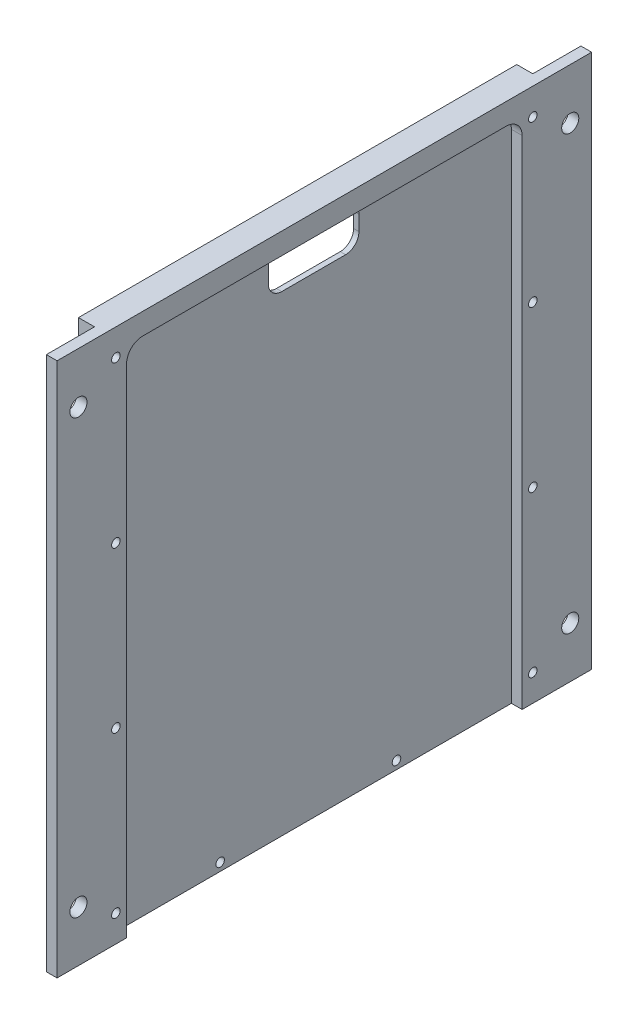
SolidWorks part; units mm, degrees
material "6061-T6 (SS)"
ref_plane "Front Plane" through (0, 0, 0) normal (0, 0, 1) x (1, 0, 0)
ref_plane "Top Plane" through (0, 0, 0) normal (0, 1, 0) x (1, 0, 0)
ref_plane "Right Plane" through (0, 0, 0) normal (1, 0, 0) x (0, 0, -1)
ref_plane "Plane1" through (4.25, 0, 0) normal (1, 0, 0) x (0, 0, -1)
sketch "Sketch1" plane through (4.25, 0, 0) normal (1, 0, 0) x (0, 0, -1)
  line L0 (-4.25, 0) -> (4.25, 0)
  line L1 (4.25, 0) -> (4.25, 227)
  line L2 (4.25, 227) -> (-4.25, 227)
  line L3 (-4.25, 227) -> (-4.25, 0)
  dimension "D1" = 227
  dimension "D2" = 8.5
  dimension "D3" = 4.25
  dimension "D4" = 227
extrude "Boss-Extrude1" add sketch "Sketch1" against normal blind 8.5
ref_plane "Plane2" through (-4.25, 0, 0) normal (-1, 0, 0) x (0, -1, 0)
sketch "Sketch2" plane through (-4.25, 0, 0) normal (-1, 0, 0) x (0, -1, 0)
  line L0 (-6.5, -87.25) -> (-6.5, -4.25)
  line L1 (-6.5, -4.25) -> (-220.5, -4.25)
  line L2 (-220.5, -4.25) -> (-220.5, -87.25)
  line L3 (-220.5, -87.25) -> (-227, -87.25)
  line L4 (-227, -87.25) -> (-227, -95.75)
  line L5 (-227, -95.75) -> (0, -95.75)
  line L6 (0, -95.75) -> (0, -87.25)
  line L7 (0, -87.25) -> (-6.5, -87.25)
  line L8 (0, -4.25) -> (-227, -4.25) construction
  dimension "D1" = 91.5
  dimension "D2" = 6.5
  dimension "D3" = 83
  dimension "D4" = 8.5
  dimension "D5" = 214
extrude "Boss-Extrude2" add sketch "Sketch2" against normal blind 2
sketch "Sketch3" plane through (-2.25, 0, 0) normal (1, 0, 0) x (0, 0, -1)
  line L0 (87.25, 0) -> (87.25, 227)
  line L1 (87.25, 227) -> (95.75, 227)
  line L2 (95.75, 227) -> (95.75, 0)
  line L3 (95.75, 0) -> (87.25, 0)
extrude "Boss-Extrude3" add sketch "Sketch3" along normal blind 6.5
ref_plane "Z_midplane" through (0, 113.5, 0) normal (0, 1, 0) x (1, 0, 0)
sketch "Sketch4" plane through (-4.25, 0, 0) normal (-1, 0, 0) x (0, 0, 1)
  line L0 (-4.75, 6.5) -> (-86.75, 6.5)
  line L1 (-86.75, 6.5) -> (-86.75, 220.5)
  line L2 (-86.75, 220.5) -> (-4.75, 220.5)
  line L3 (-4.75, 220.5) -> (-4.75, 6.5)
extrude "Boss-Extrude4" add sketch "Sketch4" along normal blind 3
sketch "Sketch5" plane through (-2.25, 0, 0) normal (1, 0, 0) x (0, 0, -1)
  line L0 (8.75, 10.5) -> (82.75, 10.5)
  line L1 (82.75, 10.5) -> (82.75, 216.5)
  line L2 (82.75, 216.5) -> (8.75, 216.5)
  line L3 (8.75, 216.5) -> (8.75, 10.5)
  line L4 (87.25, 6.5) -> (4.25, 6.5) construction
  line L5 (4.75, 6.5) -> (4.75, 220.5) construction
  line L6 (86.75, 220.5) -> (86.75, 6.5) construction
  line L7 (4.75, 220.5) -> (86.75, 220.5) construction
  dimension "D1" = 4
  dimension "D2" = 4
  dimension "D3" = 4
  dimension "D4" = 4
extrude "Cut-Extrude1" cut sketch "Sketch5" against normal through all
hole_wizard "M2x0.4 Tapped Hole1" positions "Sketch27" profile "Sketch26" tap size "M2x0.4" standard "ANSI Metric" end condition through all
sketch "Sketch27" plane through (-7.25, 0, 0) normal (-1, 0, 0) x (0, 0, 1)
  line L0 (-86.75, 6.5) -> (-4.75, 6.5) construction
  line L2 (-45.75, 10.5) -> (-45.75, 216.5) construction
  line L3 (-8.75, 10.5) -> (-82.75, 10.5) construction
  line L4 (-82.75, 216.5) -> (-8.75, 216.5) construction
  line L6 (-8.75, 113.5) -> (-82.75, 113.5) construction
  line L7 (-8.75, 216.5) -> (-8.75, 10.5) construction
  line L8 (-82.75, 10.5) -> (-82.75, 216.5) construction
  line L9 (-8.75, 11.5) -> (-4.75, 11.5) construction
  line L10 (-4.75, 6.5) -> (-4.75, 220.5) construction
  point P0 (-6.75, 11.5)
  point P31 (-6.75, 41.5)
  point P32 (-6.75, 71.5)
  point P33 (-6.75, 101.5)
  point P54 (-84.75, 11.5)
  point P55 (-84.75, 41.5)
  point P56 (-84.75, 71.5)
  point P57 (-84.75, 101.5)
  point P60 (-84.75, 125.5)
  point P61 (-84.75, 155.5)
  point P62 (-84.75, 185.5)
  point P63 (-84.75, 215.5)
  point P65 (-6.75, 125.5)
  point P66 (-6.75, 155.5)
  point P67 (-6.75, 185.5)
  point P68 (-6.75, 215.5)
  point P81 (-6.75, 11.5)
  dimension "D1" = 5
  dimension "D4" = 30
  dimension "D3" = 4
sketch "Sketch26" plane through (-7.25, 11.5, -6.75) normal (0, 1, 0) x (0, 0, 1)
  line L0 (0, 0) -> (0, 11.5)
  line L1 (0, 11.5) -> (0.8, 11.5)
  line L2 (0.8, 11.5) -> (0.8, 0)
  line L5 (0.8, 0) -> (0, 0)
  line L11 (0, -6.35) -> (0, 107.95) construction
  dimension "Thru Tap Drill Dia." = 1.6
  dimension "Thru Tap Drill Depth" = 11.5
cosmetic thread "Hole Thread1" parameters "D2"=2
cosmetic thread "Hole Thread2" parameters "D2"=2
cosmetic thread "Hole Thread3" parameters "D2"=2
cosmetic thread "Hole Thread4" parameters "D2"=2
cosmetic thread "Hole Thread5" parameters "D2"=2
cosmetic thread "Hole Thread6" parameters "D2"=2
cosmetic thread "Hole Thread7" parameters "D2"=2
cosmetic thread "Hole Thread8" parameters "D2"=2
cosmetic thread "Hole Thread9" parameters "D2"=2
cosmetic thread "Hole Thread10" parameters "D2"=2
cosmetic thread "Hole Thread11" parameters "D2"=2
cosmetic thread "Hole Thread12" parameters "D2"=2
cosmetic thread "Hole Thread13" parameters "D2"=2
cosmetic thread "Hole Thread14" parameters "D2"=2
cosmetic thread "Hole Thread15" parameters "D2"=2
cosmetic thread "Hole Thread16" parameters "D2"=2
fillet "Fillet2" radius 3 4 edges at (-4.75, 10.5, -8.75) (-4.75, 216.5, -82.75) (-4.75, 216.5, -8.75) (-4.75, 10.5, -82.75) tangent propagation no
fillet "Fillet12" radius 2 1 edges type face fillet first side face at (-6.5, 140.25, -86.75) second side face at (-4.75, 6.5, -45.8125)
ref_plane "Y_midplane" through (0, 0, -45.75) normal (0, 0, 1) x (1, 0, 0)
sketch "Sketch43" plane through (-7.25, 0, 0) normal (-1, 0, 0) x (0, 0, 1)
  line L0 (-45.75, 10.5) -> (-45.75, 216.5) construction
  line L1 (-27.75, 10.5) -> (-30.75, 10.5)
  line L2 (-27.75, 10.5) -> (-27.75, 216.5)
  line L3 (-27.75, 216.5) -> (-30.75, 216.5)
  line L4 (-30.75, 10.5) -> (-30.75, 216.5)
  line L5 (-11.75, 10.5) -> (-79.75, 10.5) construction
  line L6 (-79.75, 216.5) -> (-11.75, 216.5) construction
  line L7 (-63.75, 10.5) -> (-60.75, 10.5)
  line L8 (-63.75, 10.5) -> (-63.75, 216.5)
  line L9 (-63.75, 216.5) -> (-60.75, 216.5)
  line L10 (-60.75, 10.5) -> (-60.75, 216.5)
  dimension "D1" = 3
  dimension "D2" = 30
extrude "Boss-Extrude6" add sketch "Sketch43" against normal blind 3
sketch "Sketch44" plane through (-7.25, 0, 0) normal (-1, 0, 0) x (0, 0, 1)
  line L0 (-8.75, 213.5) -> (-8.75, 13.5) construction
  line L1 (-8.75, 35.8) -> (-82.75, 35.8)
  line L2 (-8.75, 35.8) -> (-8.75, 38.8)
  line L3 (-8.75, 38.8) -> (-82.75, 38.8)
  line L4 (-82.75, 35.8) -> (-82.75, 38.8)
  line L5 (-8.75, 75.8) -> (-82.75, 75.8)
  line L6 (-8.75, 75.8) -> (-8.75, 78.8)
  line L7 (-8.75, 78.8) -> (-82.75, 78.8)
  line L8 (-82.75, 75.8) -> (-82.75, 78.8)
  line L9 (-8.75, 103.5) -> (-82.75, 103.5)
  line L10 (-8.75, 103.5) -> (-8.75, 106.5)
  line L11 (-8.75, 106.5) -> (-82.75, 106.5)
  line L12 (-82.75, 103.5) -> (-82.75, 106.5)
  line L13 (-82.75, 13.5) -> (-82.75, 213.5) construction
  line L14 (-84.75, 6.5) -> (-4.75, 6.5) construction
  line L15 (-8.75, 113.5) -> (-82.75, 113.5) construction
  line L16 (-8.75, 191.2) -> (-8.75, 188.2)
  line L17 (-8.75, 191.2) -> (-82.75, 191.2)
  line L18 (-82.75, 191.2) -> (-82.75, 188.2)
  line L19 (-8.75, 188.2) -> (-82.75, 188.2)
  line L20 (-8.75, 151.2) -> (-8.75, 148.2)
  line L21 (-8.75, 151.2) -> (-82.75, 151.2)
  line L22 (-82.75, 151.2) -> (-82.75, 148.2)
  line L23 (-8.75, 148.2) -> (-82.75, 148.2)
  line L24 (-8.75, 123.5) -> (-8.75, 120.5)
  line L25 (-8.75, 123.5) -> (-82.75, 123.5)
  line L26 (-82.75, 123.5) -> (-82.75, 120.5)
  line L27 (-8.75, 120.5) -> (-82.75, 120.5)
  dimension "D1" = 3
  dimension "D2" = 29.3
  dimension "D3" = 40
  dimension "D4" = 100
extrude "Boss-Extrude7" add sketch "Sketch44" against normal up to surface (3 mm away) up to face at (-4.25, 113.5, -29.25)
fillet "Fillet4" radius 3 80 edges at (-5.75, 188.2, -8.75) (-5.75, 216.5, -60.75) (-5.75, 35.8, -82.75) (-5.75, 38.8, -82.75) (-5.75, 75.8, -82.75) (-5.75, 78.8, -82.75) (-5.75, 103.5, -82.75) (-5.75, 106.5, -82.75) (-5.75, 120.5, -82.75) (-5.75, 123.5, -82.75) (-5.75, 10.5, -60.75) (-5.75, 10.5, -63.75) (-5.75, 10.5, -27.75) (-5.75, 10.5, -30.75) (-5.75, 35.8, -8.75) (-5.75, 38.8, -8.75) (-5.75, 75.8, -8.75) (-5.75, 78.8, -8.75) (-5.75, 103.5, -8.75) (-5.75, 106.5, -8.75) (-5.75, 123.5, -8.75) (-5.75, 120.5, -8.75) (-5.75, 151.2, -8.75) (-5.75, 148.2, -8.75) (-5.75, 216.5, -27.75) (-5.75, 216.5, -63.75) (-5.75, 216.5, -30.75) (-5.75, 191.2, -8.75) (-5.75, 148.2, -82.75) (-5.75, 151.2, -82.75) (-5.75, 188.2, -82.75) (-5.75, 191.2, -82.75) (-5.75, 191.2, -60.75) (-5.75, 188.2, -60.75) (-5.75, 191.2, -63.75) (-5.75, 188.2, -63.75) (-5.75, 191.2, -27.75) (-5.75, 191.2, -30.75) (-5.75, 188.2, -27.75) (-5.75, 188.2, -30.75) (-5.75, 151.2, -27.75) (-5.75, 151.2, -30.75) (-5.75, 148.2, -27.75) (-5.75, 148.2, -30.75) (-5.75, 151.2, -60.75) (-5.75, 148.2, -60.75) (-5.75, 151.2, -63.75) (-5.75, 148.2, -63.75) (-5.75, 123.5, -27.75) (-5.75, 123.5, -30.75) (-5.75, 120.5, -27.75) (-5.75, 120.5, -30.75) (-5.75, 103.5, -27.75) (-5.75, 103.5, -30.75) (-5.75, 106.5, -27.75) (-5.75, 106.5, -30.75) (-5.75, 123.5, -60.75) (-5.75, 120.5, -60.75) (-5.75, 123.5, -63.75) (-5.75, 120.5, -63.75) (-5.75, 103.5, -60.75) (-5.75, 106.5, -60.75) (-5.75, 103.5, -63.75) (-5.75, 106.5, -63.75) (-5.75, 78.8, -30.75) (-5.75, 75.8, -27.75) (-5.75, 75.8, -30.75) (-5.75, 78.8, -27.75) (-5.75, 75.8, -60.75) (-5.75, 78.8, -60.75) (-5.75, 75.8, -63.75) (-5.75, 78.8, -63.75) (-5.75, 35.8, -27.75) (-5.75, 35.8, -30.75) (-5.75, 38.8, -27.75) (-5.75, 38.8, -30.75) (-5.75, 35.8, -63.75) (-5.75, 35.8, -60.75) (-5.75, 38.8, -63.75) (-5.75, 38.8, -60.75) tangent propagation no
sketch "Sketch50" plane through (-4.25, 0, 0) normal (1, 0, 0) x (0, 0, -1)
  line L0 (79.75, 216.5) -> (11.75, 216.5) construction
  line L1 (8.75, 213.5) -> (8.75, 13.5) construction
  line L2 (11.75, 10.5) -> (79.75, 10.5) construction
  line L3 (82.75, 13.5) -> (82.75, 213.5) construction
  line L4 (79.75, 216.5) -> (11.75, 216.5)
  line L5 (8.75, 213.5) -> (8.75, 13.5)
  line L6 (11.75, 10.5) -> (79.75, 10.5)
  line L7 (82.75, 13.5) -> (82.75, 213.5)
  arc A0 (82.75, 213.5) -> (79.75, 216.5) centre (79.75, 213.5) ccw construction
  arc A1 (11.75, 216.5) -> (8.75, 213.5) centre (11.75, 213.5) ccw construction
  arc A2 (8.75, 13.5) -> (11.75, 10.5) centre (11.75, 13.5) ccw construction
  arc A3 (79.75, 10.5) -> (82.75, 13.5) centre (79.75, 13.5) ccw construction
  arc A4 (82.75, 213.5) -> (79.75, 216.5) centre (79.75, 213.5) ccw
  arc A5 (11.75, 216.5) -> (8.75, 213.5) centre (11.75, 213.5) ccw
  arc A6 (8.75, 13.5) -> (11.75, 10.5) centre (11.75, 13.5) ccw
  arc A7 (79.75, 10.5) -> (82.75, 13.5) centre (79.75, 13.5) ccw
extrude "webExtrude" add sketch "Sketch50" against normal blind 1
sketch "Sketch51" plane through (-5.25, 0, 0) normal (-1, 0, 0) x (0, 0, 1)
  line L0 (-57.75, 216.5) -> (-33.75, 216.5) construction
  line L1 (-54.225, 216.5) -> (-37.275, 216.5)
  line L2 (-54.225, 216.5) -> (-54.225, 208.7)
  line L3 (-54.225, 208.7) -> (-37.275, 208.7)
  line L4 (-37.275, 216.5) -> (-37.275, 208.7)
  point P4 (-45.75, 216.5)
  dimension "D1" = 7.8
  dimension "D2" = 16.95
extrude "12pinCutout" cut sketch "Sketch51" against normal through all both and the other way through all
mirror "Mirror10" about plane through (0, 113.5, 0) normal (0, 1, 0) of "12pinCutout"
fillet "Fillet18" radius 2.5 8 edges at (-4.75, 216.5, -37.275) (-4.75, 216.5, -54.225) (-4.75, 208.7, -54.225) (-4.75, 208.7, -37.275) (-4.75, 10.5, -37.275) (-4.75, 18.3, -37.275) (-4.75, 18.3, -54.225) (-4.75, 10.5, -54.225)
hole_wizard "M2x0.4 Tapped Hole2" positions "Sketch45" profile "Sketch46" tap size "M2x0.4" standard "ANSI Metric" end condition through all
sketch "Sketch45" plane through (-7.25, 0, 0) normal (-1, 0, 0) x (0, 0, 1)
  line L0 (-44.75, 6.5) -> (-44.75, 220.5) construction
  line L1 (-84.75, 6.5) -> (-4.75, 6.5) construction
  line L20 (-4.75, 113.5) -> (-86.75, 113.5) construction
  line L21 (-4.75, 6.5) -> (-4.75, 220.5) construction
  line L23 (-62.25, 75.8) -> (-62.25, 78.8) construction
  line L24 (-79.75, 75.8) -> (-66.75, 75.8) construction
  line L25 (-66.75, 78.8) -> (-79.75, 78.8) construction
  line L27 (-60.75, 77.3) -> (-63.75, 77.3) construction
  line L28 (-60.75, 41.8) -> (-60.75, 72.8) construction
  line L29 (-63.75, 72.8) -> (-63.75, 41.8) construction
  line L30 (-79.75, 216.5) -> (-11.75, 216.5) construction
  line L31 (-87.25, 227) -> (-87.25, 0) construction
  point P2 (-61.25, 105)
  point P36 (-44.75, 6.5)
  point P68 (-28.25, 105)
  point P70 (-61.25, 122)
  point P71 (-28.25, 122)
  point P73 (-62.25, 77.3)
  point P92 (-27.25, 77.3)
  dimension "D1" = 4
  dimension "D2" = 0.5
  dimension "D3" = 16.5
  dimension "D4" = 17
sketch "Sketch46" plane through (-7.25, 105, -61.25) normal (0, 1, 0) x (0, 0, 1)
  line L0 (0, 0) -> (0, 11.5)
  line L1 (0, 11.5) -> (0.8, 11.5)
  line L2 (0.8, 11.5) -> (0.8, 0)
  line L5 (0.8, 0) -> (0, 0)
  line L11 (0, -6.35) -> (0, 107.95) construction
  dimension "Thru Tap Drill Dia." = 1.6
  dimension "Thru Tap Drill Depth" = 11.5
cosmetic thread "Hole Thread17" parameters "D2"=2
cosmetic thread "Hole Thread20" parameters "D2"=2
cosmetic thread "Hole Thread21" parameters "D2"=2
cosmetic thread "Hole Thread23" parameters "D2"=2
cosmetic thread "Hole Thread41" parameters "D2"=2
cosmetic thread "Hole Thread42" parameters "D2"=2
ref_plane "chamferStart" through (0, 212.5, 0) normal (0, 1, 0) x (1, 0, 0)
sketch "Sketch36" plane through (4.25, 0, 0) normal (1, 0, 0) x (0, 0, -1)
  line L1 (4.25, 207.45) -> (-1.25, 207.45)
  line L2 (4.25, 207.45) -> (4.25, 201.95)
  line L3 (4.25, 201.95) -> (-1.25, 201.95)
  line L4 (-1.25, 207.45) -> (-1.25, 201.95)
  line L5 (-4.25, 227) -> (-4.25, 0) construction
  line L6 (4.25, 207.45) -> (-1.25, 201.95) construction
  line L7 (4.25, 220.5) -> (87.25, 220.5) construction
  dimension "D1" = 13.05
  dimension "D2" = 5.5
  dimension "D3" = 5.5
  dimension "D4" = 8.5
extrude "Boss-Extrude5" add sketch "Sketch36" against normal up to surface (6.5 mm away) up to face at (-2.25, 12.3, -6.75)
ref_plane "Plane13" through (0, 113.5, 0) normal (0, 1, 0) x (1, 0, 0)
ref_plane "center_Y" through (0, 0, -45.75) normal (0, 0, 1) x (1, 0, 0)
ref_plane "center_Z" through (0, 113.5, 0) normal (0, 1, 0) x (1, 0, 0)
sketch "Sketch58" plane through (-2.25, 0, 0) normal (1, 0, 0) x (0, 0, -1)
  line L0 (11.75, 10.5) -> (79.75, 10.5) construction
  line L1 (43.25, 10.5) -> (48.25, 10.5)
  line L2 (43.25, 10.5) -> (43.25, 12)
  line L3 (43.25, 12) -> (48.25, 12)
  line L4 (48.25, 10.5) -> (48.25, 12)
  line L5 (87.25, 6.5) -> (4.25, 6.5) construction
  point P6 (45.75, 6.5)
  point P11 (45.75, 10.5)
  dimension "D1" = 5
  dimension "D2" = 5.5
extrude "Boss-Extrude9" add sketch "Sketch58" against normal up to surface (3 mm away) up to face at (-5.25, 18.775, -45.75)
sketch "Sketch63" plane through (0, 0, 0) normal (0, -1, 0) x (-1, 0, 0)
  line L1 (-4.25, 95.75) -> (7.9173, 95.75)
  line L2 (-4.25, 95.75) -> (-4.25, -4.25)
  line L3 (-4.25, -4.25) -> (7.9173, -4.25)
  line L4 (7.9173, 95.75) -> (7.9173, -4.25)
  dimension "D1" = 12.1673
  dimension "D2" = 100
extrude "Cut-Extrude28" cut sketch "Sketch63" against normal up to surface (120.5 mm away) up to face at (-6.25, 120.5, -45.75)
sketch "Sketch64" plane through (0, 227, 0) normal (0, 1, 0) x (1, 0, 0)
  line L1 (4.25, -4.25) -> (-12.9489, -4.25)
  line L2 (4.25, -4.25) -> (4.25, 100.8651)
  line L3 (4.25, 100.8651) -> (-12.9489, 100.8651)
  line L4 (-12.9489, -4.25) -> (-12.9489, 100.8651)
  dimension "D1" = 17.1989
  dimension "D2" = 105.1151
extrude "Cut-Extrude29" cut sketch "Sketch64" against normal up to surface (6.5 mm away) up to face at (-4.75, 220.5, -45.6875)
sketch "Sketch65" plane through (0, 220.5, 0) normal (0, 1, 0) x (1, 0, 0)
  line L1 (4.25, 95.75) -> (-2.25, 95.75)
  line L2 (4.25, 95.75) -> (4.25, 87.25)
  line L3 (4.25, 87.25) -> (-2.25, 87.25)
  line L4 (-2.25, 95.75) -> (-2.25, 87.25)
  line L5 (4.25, -4.25) -> (-2.25, -4.25)
  line L6 (4.25, -4.25) -> (4.25, 4.25)
  line L7 (4.25, 4.25) -> (-2.25, 4.25)
  line L8 (-2.25, -4.25) -> (-2.25, 4.25)
extrude "Cut-Extrude30" cut sketch "Sketch65" against normal through all
sketch "Sketch70" plane through (-2.25, 0, 0) normal (1, 0, 0) x (0, 0, -1)
  line L2 (45.75, 220.5) -> (45.75, 120.5) construction
  line L3 (95.75, 120.5) -> (95.75, 220.5) construction
  line L4 (-4.25, 220.5) -> (95.75, 220.5) construction
  line L5 (82.75, 120.5) -> (8.75, 120.5) construction
  point P2 (91.75, 130)
  point P3 (91.75, 211)
  point P12 (-0.25, 130)
  point P13 (-0.25, 211)
  dimension "D5" = 4
  dimension "D6" = 4
  dimension "D8" = 81
hole_wizard "M3 Clearance Hole2" positions "Sketch71" profile "Sketch72" hole size "M3" standard "ISO" end condition through all
sketch "Sketch71" plane through (-2.25, 0, 0) normal (1, 0, 0) x (0, 0, -1)
  point P6 (91.75, 211)
  point P9 (91.75, 130)
  point P12 (-0.25, 211)
  point P15 (-0.25, 130)
sketch "Sketch72" plane through (-2.25, 211, -91.75) normal (0, 1, 0) x (0, 0, -1)
  line L0 (0, 0) -> (0, 5)
  line L1 (0, 5) -> (1.6, 5)
  line L2 (1.6, 5) -> (1.6, 0)
  line L5 (1.6, 0) -> (0, 0)
  line L11 (0, -6.35) -> (0, 107.95) construction
  dimension "Thru Hole Dia." = 3.2
  dimension "Thru Hole Depth" = 5
equation "\"D2@Sketch56\"=\"D1@Sketch56\""
equation "\"D3@Sketch48\"=\"D2@Sketch48\""
